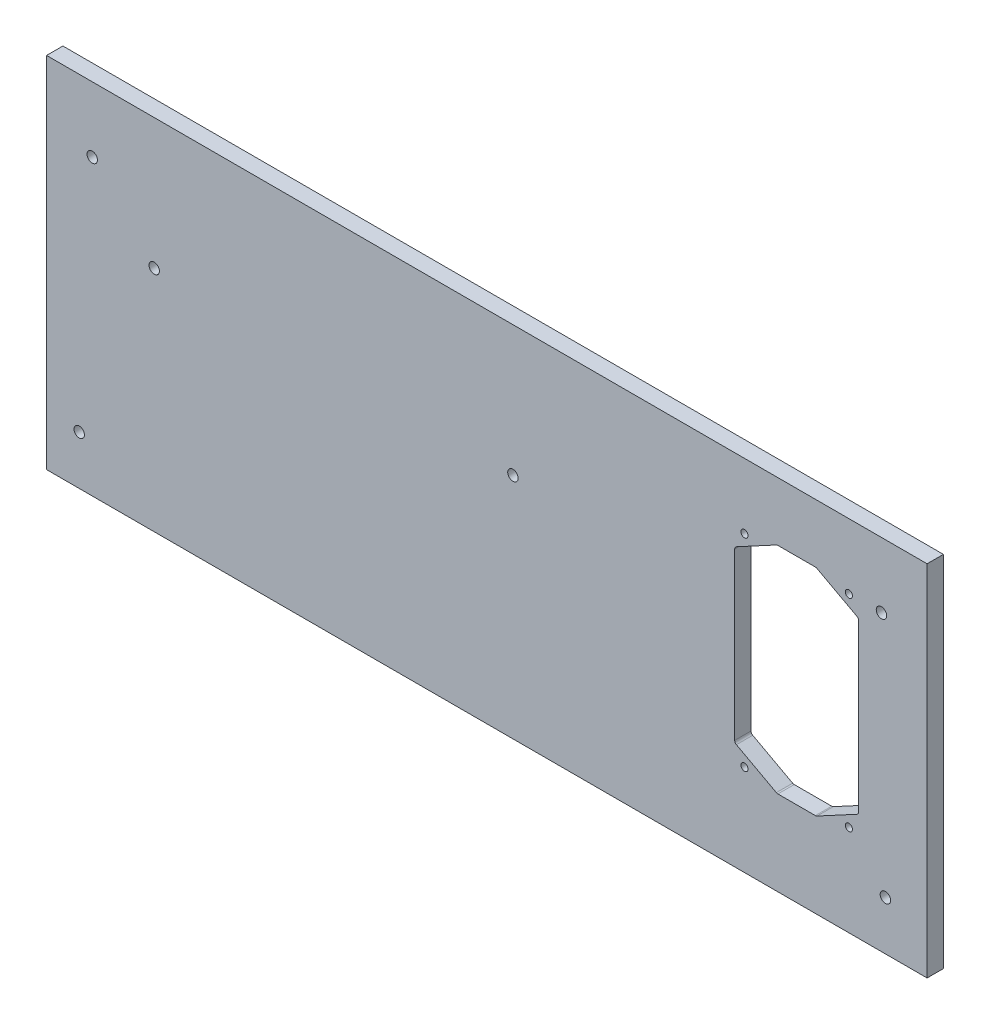
SolidWorks part; units mm, degrees
material "Polycarbonate (PC)"
ref_plane "Front Plane" through (0, 0, 0) normal (0, 0, 1) x (1, 0, 0)
ref_plane "Top Plane" through (0, 0, 0) normal (0, 1, 0) x (1, 0, 0)
ref_plane "Right Plane" through (0, 0, 0) normal (1, 0, 0) x (0, 0, -1)
sketch "Sketch1" plane through (0, 0, 0) normal (0, 0, 1) x (1, 0, 0)
  line L1 (135, -55) -> (-135, -55)
  line L2 (135, -55) -> (135, 55)
  line L3 (135, 55) -> (-135, 55)
  line L4 (-135, -55) -> (-135, 55)
  line L5 (135, -55) -> (-135, 55) construction
  line L6 (135, 55) -> (-135, -55) construction
  point P0 (0, 0)
  dimension "D1" = 110
  dimension "D2" = 270
extrude "Sheet" add sketch "Sketch1" along normal mid plane 5
sketch "Sketch4" plane through (0, 0, -2.5) normal (0, 0, -1) x (-1, 0, 0)
  line L0 (-101, 37) -> (-114, 30)
  line L1 (-89, -29) -> (-101, -29)
  line L2 (-76, -22) -> (-76, 30)
  line L3 (-89, 37) -> (-101, 37)
  line L4 (-114, -22) -> (-114, 30)
  line L5 (-76, -29) -> (-114, 37) construction
  line L6 (-76, 37) -> (-114, -29) construction
  line L7 (-79, -27) -> (-111, -27) construction
  line L8 (-79, -27) -> (-79, 35) construction
  line L9 (-79, 35) -> (-111, 35) construction
  line L10 (-111, -27) -> (-111, 35) construction
  line L11 (-79, -27) -> (-111, 35) construction
  line L12 (-79, 35) -> (-111, -27) construction
  line L13 (-101, -29) -> (-114, -22)
  line L14 (-95, 4) -> (-95, 17.8562) construction
  line L15 (-76, 30) -> (-89, 37)
  line L16 (-76, -22) -> (-89, -29)
  line L17 (-135, -55) -> (-135, 55) construction
  line L18 (135, -55) -> (-135, -55) construction
  circle A0 centre (-79, 35) radius 1.1
  circle A1 centre (-111, 35) radius 1.1
  circle A2 centre (-111, -27) radius 1.1
  circle A3 centre (-79, -27) radius 1.1
  point P0 (-95, 4)
  point P14 (-95, 4)
  dimension "D1" = 2.2
  dimension "D2" = 62
  dimension "D3" = 32
  dimension "D4" = 38
  dimension "D5" = 66
  dimension "D6" = 13
  dimension "D7" = 7
  dimension "D8" = 13
  dimension "D9" = 7
  dimension "D10" = 7
  dimension "D11" = 13
  dimension "D12" = 13
  dimension "D13" = 7
  dimension "D14" = 40
  dimension "D15" = 59
extrude "Cut-Extrude1" cut sketch "Sketch4" against normal through all
fillet "Fillet1" radius 1 8 edges at (76, 30, 0) (89, -29, 0) (101, -29, 0) (114, -22, 0) (114, 30, 0) (101, 37, 0) (89, 37, 0) (76, -22, 0)
hole_wizard "Ø3.2 (3.2) MountHoles" positions "Sketch5" profile "Sketch6" hole size "Ø3.2" standard "ANSI Metric" end condition through all
sketch "Sketch5" plane through (0, 0, -2.5) normal (0, 0, -1) x (-1, 0, 0)
  line L0 (135, -55) -> (-135, -55) construction
  line L1 (135, 55) -> (135, -55) construction
  line L2 (-135, 55) -> (135, 55) construction
  line L3 (-135, -55) -> (-135, 55) construction
  point P0 (-121, 35)
  point P2 (-122.2168, -40)
  point P4 (125, -40)
  point P6 (121, 35)
  dimension "D1" = 15
  dimension "D2" = 10
  dimension "D3" = 20
  dimension "D4" = 14
  dimension "D5" = 14
sketch "Sketch6" plane through (121, 35, -2.5) normal (1, 0, 0) x (0, 1, 0)
  line L0 (0, 0) -> (0, 5)
  line L1 (0, 5) -> (1.6, 5)
  line L2 (1.6, 5) -> (1.6, 1.65)
  line L3 (1.6, 1.65) -> (3.25, 0)
  line L5 (3.25, 0) -> (0, 0)
  line L6 (-1.6, 1.65) -> (-3.25, 0) construction
  line L11 (0, -6.35) -> (0, 107.95) construction
  dimension "Thru Hole Dia." = 3.2
  dimension "Thru Hole Depth" = 5
  dimension "Near C'Sink Dia." = 6.5
  dimension "Near C'Sink Angle" = 90
hole_wizard "Ø3.2 (3.2) MiddlePartHoles" positions "Sketch7" profile "Sketch8" hole size "Ø3.2" standard "ANSI Metric" end condition through all
sketch "Sketch7" plane through (0, 0, -2.5) normal (0, 0, -1) x (-1, 0, 0)
  line L0 (135, 55) -> (135, -55) construction
  line L1 (-135, 55) -> (135, 55) construction
  point P0 (-8, 15)
  point P2 (102, 15)
  dimension "D1" = 33
  dimension "D2" = 110
  dimension "D3" = 40
sketch "Sketch8" plane through (8, 15, -2.5) normal (1, 0, 0) x (0, 1, 0)
  line L0 (0, 0) -> (0, 5)
  line L1 (0, 5) -> (1.6, 5)
  line L2 (1.6, 5) -> (1.6, 1.65)
  line L3 (1.6, 1.65) -> (3.25, 0)
  line L5 (3.25, 0) -> (0, 0)
  line L6 (-1.6, 1.65) -> (-3.25, 0) construction
  line L11 (0, -6.35) -> (0, 107.95) construction
  dimension "Thru Hole Dia." = 3.2
  dimension "Thru Hole Depth" = 5
  dimension "Near C'Sink Dia." = 6.5
  dimension "Near C'Sink Angle" = 90
equation "\"D5@Sketch5\"=\"D4@Sketch5\""
